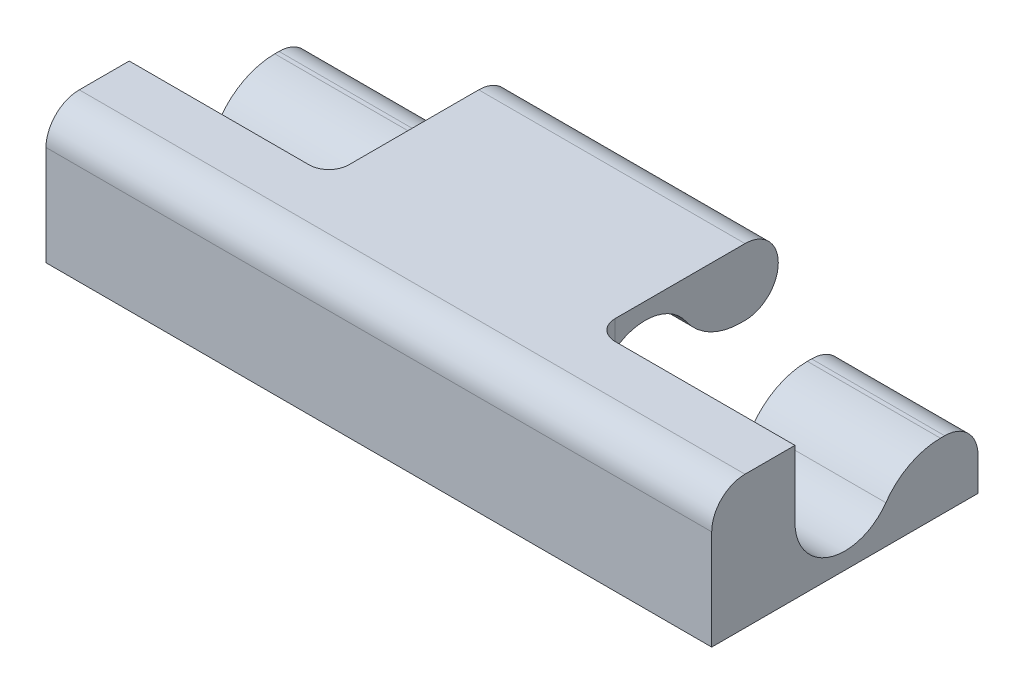
SolidWorks part; units mm, degrees
ref_plane "Plan de face" through (0, 0, 0) normal (0, 0, 1) x (1, 0, 0)
ref_plane "Plan de dessus" through (0, 0, 0) normal (0, 1, 0) x (1, 0, 0)
ref_plane "Plan de droite" through (0, 0, 0) normal (1, 0, 0) x (0, 0, -1)
sketch "Esquisse1" plane through (0, 0, 0) normal (0, 1, 0) x (1, 0, 0)
  line L1 (-5, -2) -> (5, -2)
  line L2 (-5, -2) -> (-5, 2)
  line L3 (-5, 2) -> (5, 2)
  line L4 (5, -2) -> (5, 2)
  line L5 (-5, -2) -> (5, 2) construction
  line L6 (-5, 2) -> (5, -2) construction
  point P0 (0, 0)
  dimension "D1" = 10
  dimension "D2" = 4
extrude "Boss.-Extru.1" add sketch "Esquisse1" along normal blind 2
sketch "Esquisse2" plane through (5, 0, 0) normal (1, 0, 0) x (0, 0, -1)
  line L0 (-2, 0) -> (2, 0) construction
  circle A0 centre (0, 1) radius 0.75
  point P2 (0, 0)
  dimension "D1" = 1.5
  dimension "D2" = 1
extrude "Enlèv. mat.-Extru.1" cut sketch "Esquisse2" against normal blind 10 contours A0
ref_plane "milieu" through (0, 0, 0) normal (-1, 0, 0) x (0, 0, 1)
sketch "Esquisse7" plane through (-5, 0, 0) normal (-1, 0, 0) x (0, 0, 1)
  line L4 (-2, 2) -> (-2, 0) construction
  line L5 (-2, 1) -> (-2, 2)
  line L6 (-2, 1) -> (0.75, 1)
  line L7 (0.75, 1) -> (0.75, 2)
  line L8 (-2, 2) -> (2, 2) construction
  line L9 (0.75, 2) -> (-2, 2)
  circle A0 centre (0, 1) radius 0.75 construction
extrude "Enlèv. mat.-Extru.3" cut sketch "Esquisse7" against normal blind 3
mirror "Symétrie1" about plane through (0, 0, 0) normal (-1, 0, 0) of "Enlèv. mat.-Extru.3"
sketch "Esquisse8" plane through (0, 0, 0) normal (0, -1, 0) x (1, 0, 0)
  line L3 (5, -2) -> (-5, -2) construction
  line L4 (-3, -2) -> (0, -2)
  line L6 (-3, -2) -> (-3, 0.75)
  line L7 (-3, 0.75) -> (0, 0.75)
  line L8 (0, 0.75) -> (0, -2)
  dimension "D1" = 3
  dimension "D2" = 2.75
extrude "Enlèv. mat.-Extru.5" cut sketch "Esquisse8" against normal up to vertex (1 mm away) up to point (-2, 1, -2)
mirror "Symétrie3" about plane through (0, 0, 0) normal (-1, 0, 0) of "Enlèv. mat.-Extru.5"
fillet "Congé1" radius 1 3 edges at (4, 1, -0.75) (0, 1, -0.75) (-4, 1, -0.75)
fillet "Congé2" radius 0.5 3 edges at (-4, 1, -2) (0, 1, -2) (4, 1, -2)
fillet "Congé3" radius 0.5 2 edges at (0, 2, -2) (0, 2, 2)
fillet "Congé4" radius 0.3 4 edges at (3, 0.5, 0.75) (2, 1.5, 0.75) (-2, 1.5, 0.75) (-3, 0.5, 0.75)
